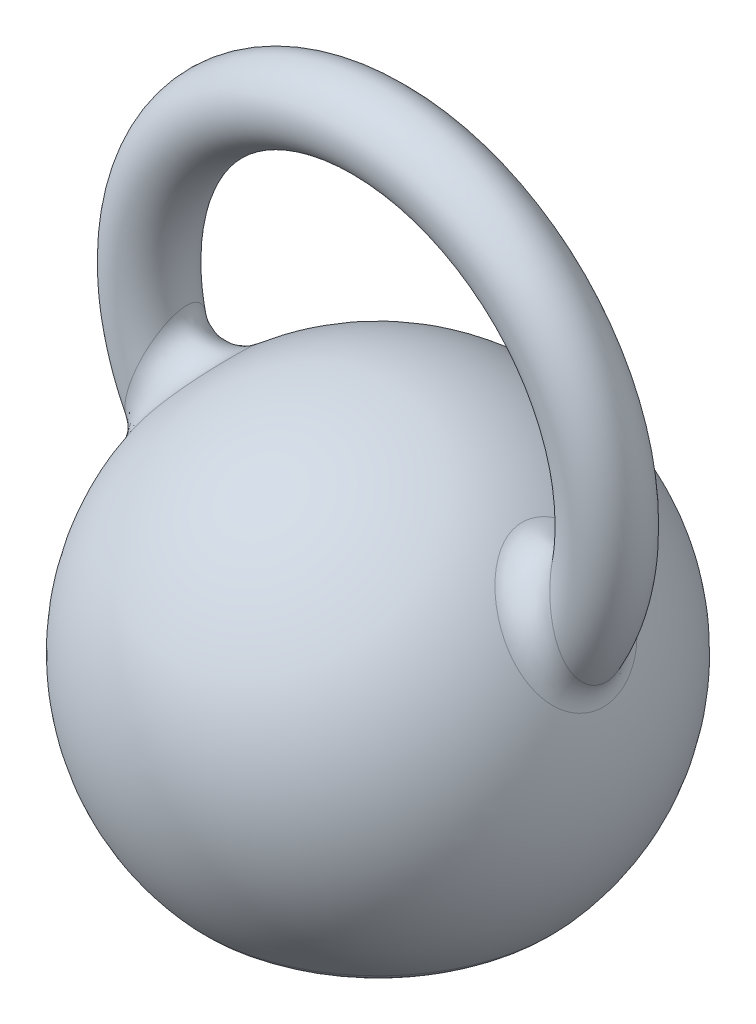
SolidWorks part; units mm, degrees
material "Cast Alloy Steel"
ref_plane "Front Plane" through (0, 0, 0) normal (0, 0, 1) x (1, 0, 0)
ref_plane "Top Plane" through (0, 0, 0) normal (0, 1, 0) x (1, 0, 0)
ref_plane "Right Plane" through (0, 0, 0) normal (1, 0, 0) x (0, 0, -1)
sketch "Sketch1" plane through (0, 0, 0) normal (0, 0, 1) x (1, 0, 0)
  line L0 (0, -101.6) -> (0, 101.6) construction
  line L1 (0, -76.2) -> (67.2021, -76.2)
  line L2 (0, 101.6) -> (0, -76.2)
  line L3 (0, 101.6) -> (-97.0776, 101.6) construction
  line L4 (0, 0) -> (101.6, 0) construction
  ellipse E0 centre (0, 0) end of major axis (0, 101.6) minor radius 101.6 (67.2021, -76.2) -> (0, 101.6) ccw
  point P4 (0, 0)
  dimension "D1" = 101.6
  dimension "D2" = 177.8
revolve "Revolve1" add sketch "Sketch1" angle 360 about L0
fillet "Fillet1" radius 25.4 1 edges at (67.2021, -76.2, 0)
sketch "Sketch2" plane through (0, 0, 0) normal (0, 0, 1) x (1, 0, 0)
  line L0 (0, 0) -> (0, 196.4885) construction
  line L1 (0, 196.4885) -> (-45.1729, 196.4885) construction
  arc A0 (0, 196.4885) -> (78.4036, 36.5845) centre (0, 97.3152) cw
ref_plane "Plane1" through (78.4036, 36.5845, 0) normal (-0.6124, -0.7906, 0) x (-0.7906, 0.6124, 0)
sketch "Sketch3" plane through (78.4036, 36.5845, 0) normal (-0.6124, -0.7906, 0) x (-0.7906, 0.6124, 0)
  line L0 (0, 0) -> (159.904, 0) construction
  circle A0 centre (0, 0) radius 15.875
  dimension "D1" = 31.75
sweep "Sweep1" add profiles "Sketch3" path "Sketch2"
mirror "Mirror1" about plane through (0, 0, 0) normal (1, 0, 0) of "Sweep1"
fillet "Fillet2" radius 12.7 2 edges at (77.359, 65.8095, 2.6943) (-95.6294, 34.1212, 3.6492)
sketch "Sketch4" plane through (0, -76.2, 0) normal (0, -1, 0) x (1, 0, 0)
  circle A0 centre (0, 0) radius 62.1774
extrude "Cut-Extrude1" cut sketch "Sketch4" against normal blind 26.416 and the other way through all
